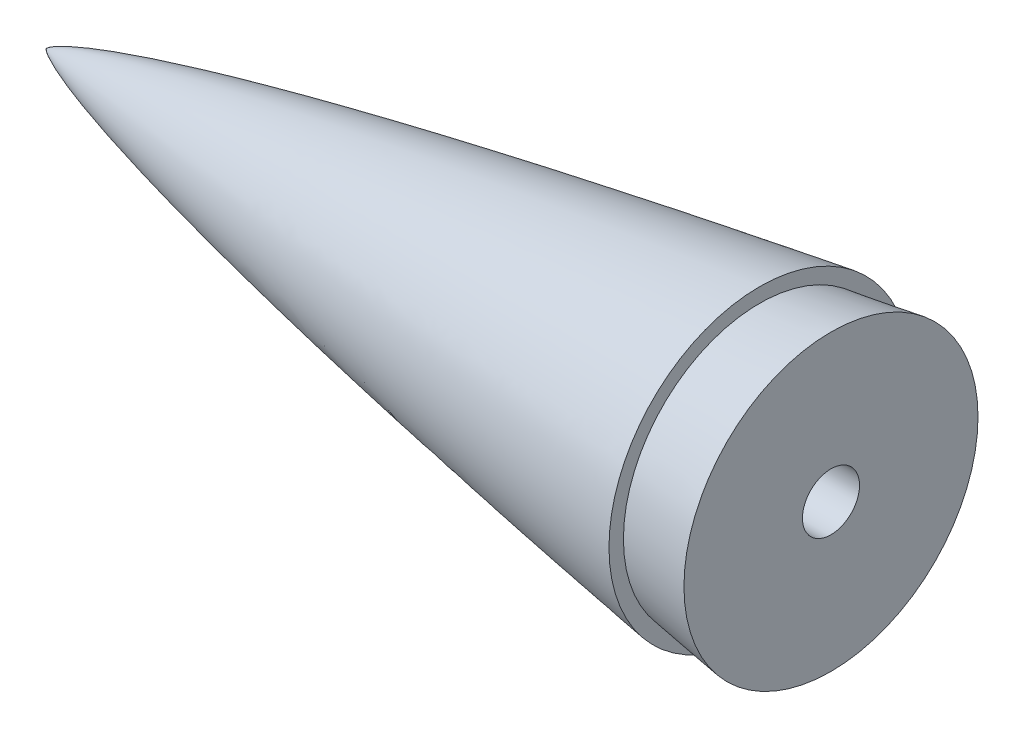
SolidWorks part; units mm, degrees
material "6061-T6 (SS)"
ref_plane "Front Plane" through (0, 0, 0) normal (0, 0, 1) x (1, 0, 0)
ref_plane "Top Plane" through (0, 0, 0) normal (0, 1, 0) x (1, 0, 0)
ref_plane "Right Plane" through (0, 0, 0) normal (1, 0, 0) x (0, 0, -1)
sketch "Sketch3" plane through (0, 0, 0) normal (0, 0, 1) x (1, 0, 0)
  line L0 (0, 0) -> (750, 0) construction
  line L1 (750, 75) -> (750, 0) construction
  line L4 (100, 0) -> (100, 21.1151) construction
  line L5 (98, 12.678) -> (98, 0)
  line L8 (110, 18.783) -> (110, 20.6076)
  line L9 (110, 18.783) -> (98, 18.783) construction
  line L10 (110, 20.6076) -> (100, 19.0916)
  line L11 (100, 19.0916) -> (100, 21.1151)
  line L12 (0, 0) -> (4.5526, 0)
  line L13 (4.5526, 0) -> (92.0147, 17.5799)
  line L14 (98, 0) -> (110, 0)
  line L15 (110, 0) -> (110, 18.783)
  arc A0 (98, 12.678) -> (92.0147, 17.5799) centre (93, 12.678) ccw
  spline S0 degree 4 poles (0, 0) (0.0027, 0.0074) (0.0091, 0.0215) (0.0269, 0.047) (0.0684, 0.0933) (0.1314, 0.151) (0.2168, 0.2183) (0.3382, 0.3041) (0.4839, 0.3974) (0.6551, 0.4981) (0.8516, 0.6056) (1.1377, 0.7534) (1.5815, 0.9661) (2.3351, 1.2961) (3.6829, 1.8266) (6.1115, 2.6745) (10.5746, 4.038) (18.9517, 6.252) (33.5701, 9.5653) (58.4067, 14.4079) (92.5079, 20.1209) (133.842, 26.2251) (179.8092, 32.3065) (225.8421, 37.8632) (271.9254, 42.9839) (318.0491, 47.7253) (364.2071, 52.1207) (410.3947, 56.191) (456.6091, 59.9459) (502.848, 63.3865) (549.1098, 66.5042) (595.3934, 69.2798) (635.9102, 71.3773) (670.652, 72.8985) (698.6683, 73.9066) (717.5285, 74.458) (733.0226, 74.8041) (742.7236, 74.948) (747.5745, 74.994) (750, 75) knots 0 0 0 0 0 0.000041 0.000082 0.000164 0.000329 0.000493 0.000658 0.000951 0.001245 0.001545 0.001844 0.002657 0.003853 0.005902 0.009516 0.016281 0.028569 0.051794 0.088907 0.150314 0.211721 0.273128 0.334535 0.395942 0.457348 0.518755 0.580162 0.641569 0.702976 0.764383 0.825789 0.887196 0.9179 0.948603 0.974302 0.987151 1 1 1 1 1 construction
  spline S1 degree 4 poles (0, 0) (0.0027, 0.0074) (0.0091, 0.0215) (0.0269, 0.047) (0.0684, 0.0933) (0.1314, 0.151) (0.2168, 0.2183) (0.3382, 0.3041) (0.4839, 0.3974) (0.6551, 0.4981) (0.8516, 0.6056) (1.1377, 0.7534) (1.5815, 0.9661) (2.3351, 1.2961) (3.6829, 1.8266) (6.1115, 2.6745) (10.5746, 4.038) (18.9517, 6.252) (33.5701, 9.5653) (58.4067, 14.4079) (92.5079, 20.1209) (133.842, 26.2251) (179.8092, 32.3065) (225.8421, 37.8632) (271.9254, 42.9839) (318.0491, 47.7253) (364.2071, 52.1207) (410.3947, 56.191) (456.6091, 59.9459) (502.848, 63.3865) (549.1098, 66.5042) (595.3934, 69.2798) (635.9102, 71.3773) (670.652, 72.8985) (698.6683, 73.9066) (717.5285, 74.458) (733.0226, 74.8041) (742.7236, 74.948) (747.5745, 74.994) (750, 75) knots 0 0 0 0 0 0.000041 0.000082 0.000164 0.000329 0.000493 0.000658 0.000951 0.001245 0.001545 0.001844 0.002657 0.003853 0.005902 0.009516 0.016281 0.028569 0.051794 0.088907 0.150314 0.211721 0.273128 0.334535 0.395942 0.457348 0.518755 0.580162 0.641569 0.702976 0.764383 0.825789 0.887196 0.9179 0.948603 0.974302 0.987151 1 1 1 1 1 construction
  spline S2 degree 1 poles (1.4903, -1.3338) (750.005, 73) knots 0 0 1 1 construction
  spline S3 degree 3 poles (1.4903, -1.3338) (1.5589, -1.2901) (1.6884, -1.215) (2.0463, -1.0265) (2.5333, -0.7992) (3.1596, -0.5329) (3.7794, -0.2875) (4.3018, -0.0911) (4.7453, 0.0703) (5.4421, 0.3177) (6.9404, 0.8231) (9.2452, 1.5349) (12.978, 2.5975) (17.6948, 3.8203) (23.3974, 5.1816) (29.1253, 6.4628) (36.7889, 8.0882) (46.4017, 9.997) (57.9721, 12.1425) (69.5671, 14.1772) (81.1803, 16.1199) (90.4946, 17.6132) (96.2699, 18.5152) (98.3333, 18.8346) (99, 18.9375) (99.6666, 19.0403) (101.3329, 19.2967) (103.9991, 19.7041) (107.9992, 20.3091) (112.0334, 20.9118) (122.6706, 22.482) (139.4233, 24.8657) (162.7777, 28.0087) (193.9457, 31.9976) (232.9503, 36.6516) (279.809, 41.7958) (326.7103, 46.554) (373.6471, 50.959) (420.6145, 55.0304) (483.2742, 60.024) (545.9829, 64.3695) (608.7338, 67.9946) (655.8157, 70.3049) (695.0668, 71.8209) (722.5426, 72.5832) (738.2468, 72.8875) (746.0841, 72.9903) (750.005, 73) knots 0.00073 0.00073 0.00073 0.00073 0.001218 0.001706 0.002682 0.003658 0.004634 0.005493 0.00598 0.006585 0.008537 0.01244 0.016344 0.02415 0.031957 0.039764 0.047571 0.063184 0.078798 0.094412 0.110025 0.125639 0.13193 0.133272 0.133942 0.134613 0.135954 0.140646 0.145339 0.152042 0.156866 0.188093 0.21932 0.250548 0.313002 0.375456 0.437911 0.500365 0.562819 0.625274 0.750183 0.812637 0.875091 0.937546 0.968773 0.984386 1 1 1 1 construction
  spline S4 degree 4 poles (0, 0) (0.0027, 0.0074) (0.0091, 0.0215) (0.0269, 0.047) (0.0684, 0.0933) (0.1314, 0.151) (0.2168, 0.2183) (0.3382, 0.3041) (0.4839, 0.3974) (0.6551, 0.4981) (0.8516, 0.6056) (1.1377, 0.7534) (1.5815, 0.9661) (2.3351, 1.2961) (3.6829, 1.8266) (6.1115, 2.6745) (10.5746, 4.038) (18.9517, 6.252) (33.5701, 9.5653) (58.4067, 14.4079) (92.5079, 20.1209) (133.842, 26.2251) (179.8092, 32.3065) (225.8421, 37.8632) (271.9254, 42.9839) (318.0491, 47.7253) (364.2071, 52.1207) (410.3947, 56.191) (456.6091, 59.9459) (502.848, 63.3865) (549.1098, 66.5042) (595.3934, 69.2798) (635.9102, 71.3773) (670.652, 72.8985) (698.6683, 73.9066) (717.5285, 74.458) (733.0226, 74.8041) (742.7236, 74.948) (747.5745, 74.994) (750, 75) knots 0 0 0 0 0 0.000041 0.000082 0.000164 0.000329 0.000493 0.000658 0.000951 0.001245 0.001545 0.001844 0.002657 0.003853 0.005902 0.009516 0.016281 0.028569 0.051794 0.088907 0.150314 0.211721 0.273128 0.334535 0.395942 0.457348 0.518755 0.580162 0.641569 0.702976 0.764383 0.825789 0.887196 0.9179 0.948603 0.974302 0.987151 1 1 1 1 1 construction
  spline S5 degree 4 poles (0, 0) (0.0027, 0.0074) (0.0091, 0.0215) (0.0269, 0.047) (0.0684, 0.0933) (0.1314, 0.151) (0.2168, 0.2183) (0.3382, 0.3041) (0.4839, 0.3974) (0.6551, 0.4981) (0.8516, 0.6056) (1.1377, 0.7534) (1.5815, 0.9661) (2.3351, 1.2961) (3.6829, 1.8266) (6.1115, 2.6745) (10.5746, 4.038) (18.9517, 6.252) (33.5701, 9.5653) (55.697, 13.8796) (75.6307, 17.2845) (91.2713, 19.7734) (100, 21.1151) knots 0 0 0 0 0 0.000041 0.000082 0.000164 0.000329 0.000493 0.000658 0.000951 0.001245 0.001545 0.001844 0.002657 0.003853 0.005902 0.009516 0.016281 0.028569 0.051794 0.088907 0.135691 0.135691 0.135691 0.135691 0.135691
  point P13 (110, 18.4844)
  dimension "D7" = 5
  dimension "D1" = 75
  dimension "D2" = 750
  dimension "D4" = 100
  dimension "D5" = 2
  dimension "D6" = 10
  dimension "D3" = 2
revolve "Revolve2" add sketch "Sketch3" angle 360 about L0
sketch "Sketch5" plane through (110, 0, 0) normal (1, 0, 0) x (0, 0, -1)
  point P0 (0, 0)
hole_wizard "Ø8.0 (8) Diameter Hole1" positions "3DSketch1" profile "Sketch4" hole size "Ø8.0" standard "ISO"
sketch3d "3DSketch1"
  point P0 (110, 0, 0)
  point P1 (110, 0, 0)
sketch "Sketch4" plane through (110, 0, 0) normal (0, 1, 0) x (0, 0, -1)
  line L0 (0, 0) -> (0, 23.9569)
  line L1 (0, 23.9569) -> (4, 14.3)
  line L2 (4, 14.3) -> (4, 0)
  line L5 (4, 0) -> (0, 0)
  line L10 (0, 23.9569) -> (-4, 14.3) construction
  line L11 (0, -6.35) -> (0, 107.95) construction
  dimension "Hole Dia." = 8
  dimension "Hole Depth" = 14.3
  dimension "Drill Angle" = 45
